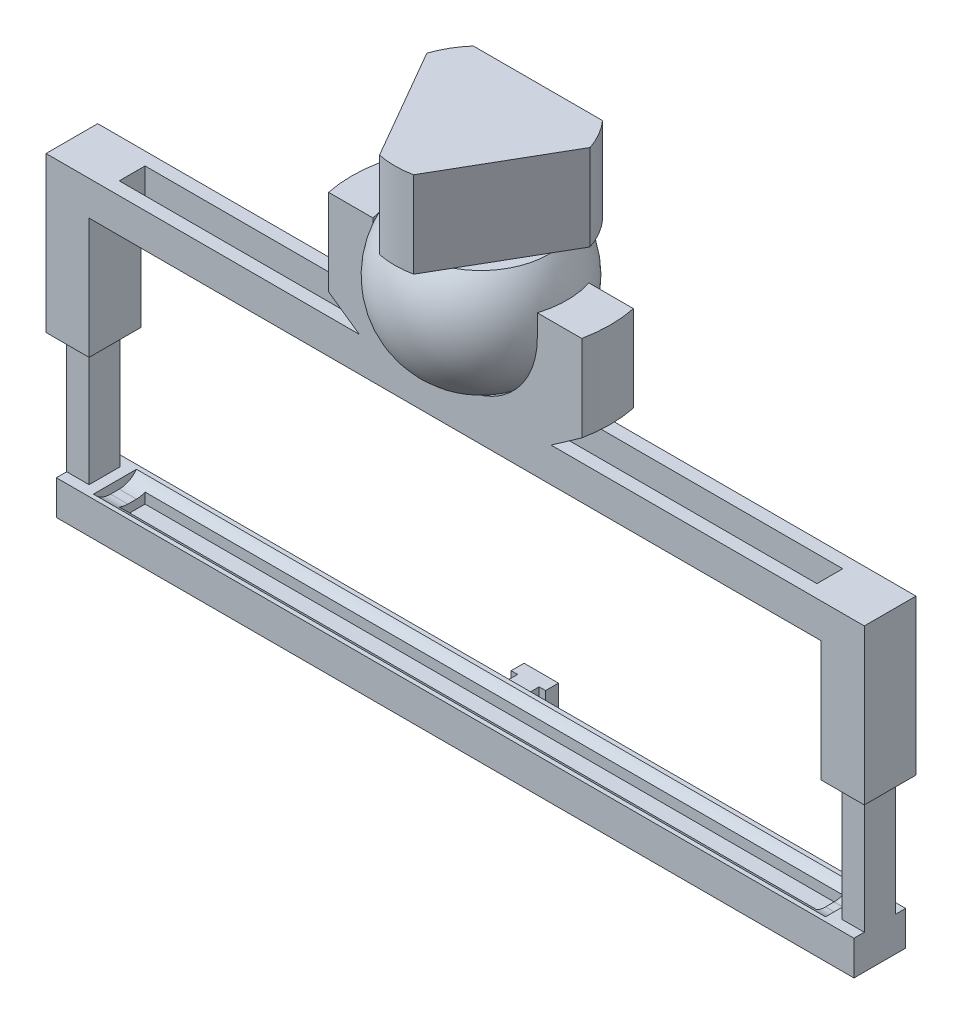
SolidWorks part; units mm, degrees
ref_plane "Front Plane" through (0, 0, 0) normal (0, 0, 1) x (1, 0, 0)
ref_plane "Top Plane" through (0, 0, 0) normal (0, 1, 0) x (1, 0, 0)
ref_plane "Right Plane" through (0, 0, 0) normal (1, 0, 0) x (0, 0, -1)
sketch "Sketch2" plane through (0, 0, 0) normal (0, 0, 1) x (1, 0, 0)
  line L0 (0, 28) -> (0, 0) construction
  line L1 (-85, 36) -> (85, 36)
  line L2 (-85, 36) -> (-85, 28)
  line L3 (-85, 28) -> (85, 28)
  line L4 (85, 36) -> (85, 28)
  line L5 (-85, 28) -> (-85, 0) construction
  line L6 (-85, 0) -> (85, 0) construction
  line L7 (85, 0) -> (85, 28) construction
  point P4 (0, 28)
  dimension "D1" = 170
  dimension "D2" = 8
  dimension "D3" = 28
extrude "Boss-Extrude1" add sketch "Sketch2" along normal mid plane 12
sketch "Sketch3" plane through (0, 28, 0) normal (0, -1, 0) x (1, 0, 0)
  line L1 (-85, 5) -> (85, 5)
  line L2 (-85, 5) -> (-85, -5)
  line L3 (-85, -5) -> (85, -5)
  line L4 (85, 5) -> (85, -5)
  line L6 (-85, 6) -> (-85, -6) construction
  line L7 (85, 6) -> (85, -6) construction
  point P6 (85, 0)
  dimension "D1" = 10
extrude "Cut-Extrude1" cut sketch "Sketch3" against normal blind 2
fillet "Fillet1" radius 5 2 edges at (0, 30, -5) (0, 30, 5)
mirror "Mirror3" about plane through (0, 0, 0) normal (0, 1, 0) of bodies 103
sketch "Sketch4" plane through (0, 36, 0) normal (0, 1, 0) x (1, 0, 0)
  line L0 (-85, -6) -> (-85, 6) construction
  line L1 (-81, 3) -> (81, 3)
  line L2 (-81, 3) -> (-81, -3)
  line L3 (-81, -3) -> (81, -3)
  line L4 (81, 3) -> (81, -3)
  line L5 (85, -6) -> (85, 6) construction
  line L6 (85, 6) -> (-85, 6) construction
  point P8 (81, 0)
  point P9 (85, 0)
  dimension "D1" = 4
  dimension "D2" = 4
  dimension "D3" = 3
extrude "Cut-Extrude2" cut sketch "Sketch4" against normal up to surface (72 mm away) up to face at (0, -36, 0)
sketch "Sketch10" plane through (85, 0, 0) normal (1, 0, 0) x (0, 0, -1)
  line L0 (6, 28) -> (6, 36) construction
  line L1 (-6, 36) -> (6, 36)
  line L2 (-6, 36) -> (-6, 0)
  line L3 (-6, 0) -> (6, 0)
  line L4 (6, 36) -> (6, 0)
extrude "Boss-Extrude6" add sketch "Sketch10" along normal blind 10
sketch "Sketch11" plane through (0, 0, 0) normal (0, -1, 0) x (1, 0, 0)
  line L8 (87, 4) -> (87, -4)
  line L9 (87, -4) -> (93, -4)
  line L10 (93, -4) -> (93, 4)
  line L11 (93, 4) -> (87, 4)
  line L12 (87, 4) -> (87, -4)
  line L13 (87, -4) -> (93, -4)
  line L14 (93, -4) -> (93, 4)
  line L15 (93, 4) -> (87, 4)
  dimension "D1" = 2
extrude "Cut-Extrude4" cut sketch "Sketch11" against normal blind 20
ref_plane "Plane2" through (0, 19, 0) normal (0, -1, 0) x (-1, 0, 0)
sketch "Sketch12" plane through (0, 19, 0) normal (0, -1, 0) x (-1, 0, 0)
  line L8 (-92.6, -3.6) -> (-87.4, -3.6)
  line L9 (-87.4, -3.6) -> (-87.4, 3.6)
  line L10 (-87.4, 3.6) -> (-92.6, 3.6)
  line L11 (-92.6, 3.6) -> (-92.6, -3.6)
  line L12 (-92.6, -3.6) -> (-87.4, -3.6)
  line L13 (-87.4, -3.6) -> (-87.4, 3.6)
  line L14 (-87.4, 3.6) -> (-92.6, 3.6)
  line L15 (-92.6, 3.6) -> (-92.6, -3.6)
  dimension "D1" = 0.4
extrude "Boss-Extrude7" add sketch "Sketch12" along normal up to surface (55 mm away) separate body up to face at (0, -36, 0)
sketch "Sketch13" plane through (0, -36, 0) normal (0, -1, 0) x (1, 0, 0)
  line L0 (92.6, 3.6) -> (92.6, -3.6) construction
  line L1 (85, 6) -> (92.6, 6)
  line L2 (85, 6) -> (85, -6)
  line L3 (85, -6) -> (92.6, -6)
  line L4 (92.6, 6) -> (92.6, -6)
extrude "Boss-Extrude8" add sketch "Sketch13" against normal up to surface (8 mm away) contours L1 L4 L3 L2 up to face at (0, -28, -5.5)
mirror "Mirror4" about plane through (0, 0, 0) normal (1, 0, 0) of "Cut-Extrude4", "Boss-Extrude6"
mirror "Mirror7" about plane through (0, 0, 0) normal (1, 0, 0) of "Boss-Extrude8"
mirror "Mirror9" about plane through (0, 0, 0) normal (1, 0, 0) of bodies 117
sketch "Sketch16" plane through (0, 36, 0) normal (0, 1, 0) x (1, 0, 0)
  line L0 (-2.5, 6) -> (2.5, 6)
  line L14 (95, 6) -> (-95, 6) construction
  line L15 (2.5, 6) -> (2.5, 11)
  line L16 (2.5, 11) -> (4, 11)
  line L17 (4, 11) -> (4, 14)
  line L18 (4, 14) -> (-4, 14)
  line L19 (-4, 14) -> (-4, 11)
  line L20 (-4, 11) -> (-2.5, 11)
  line L21 (-2.5, 11) -> (-2.5, 6)
  point P4 (0, 6)
  point P11 (0, 14)
  dimension "D1" = 5
  dimension "D2" = 3
  dimension "D3" = 5
  dimension "D4" = 8
extrude "Boss-Extrude9" add sketch "Sketch16" against normal up to surface (72 mm away)
sketch "Sketch17" plane through (0, 0, -14) normal (0, 0, -1) x (-1, 0, 0)
  line L0 (-4, -36) -> (-4, 36) construction
  line L1 (-4, 31) -> (4, 31)
  line L2 (-4, 31) -> (-4, -31)
  line L3 (-4, -31) -> (4, -31)
  line L4 (4, 31) -> (4, -31)
  line L5 (4, -36) -> (4, 36) construction
  line L6 (-4, 36) -> (4, 36) construction
  dimension "D1" = 5
  dimension "D2" = 5
extrude "Cut-Extrude5" cut sketch "Sketch17" against normal up to surface (8 mm away) up to face at (60.8333, 21.3333, -6)
sketch "Sketch18" plane through (0, 36, 0) normal (0, 1, 0) x (1, 0, 0)
  line L0 (-5, 6.5) -> (-5, 14.5)
  line L1 (-5, 14.5) -> (5, 14.5)
  line L2 (5, 14.5) -> (5, 6.5)
  line L3 (-2.5, 6) -> (-95, 6) construction
  line L4 (4, 14) -> (-4, 14) construction
  line L5 (4, 11) -> (4, 14) construction
  line L6 (-6.5, 6.5) -> (-6.5, 16)
  line L7 (-6.5, 16) -> (6.5, 16)
  line L8 (6.5, 16) -> (6.5, 6.5)
  line L9 (-6.5, 6.5) -> (-5, 6.5)
  line L10 (5, 6.5) -> (6.5, 6.5)
  point P4 (0, 14.5)
  dimension "D1" = 0.5
  dimension "D2" = 0.5
  dimension "D3" = 1
  dimension "D4" = 1.5
extrude "Boss-Extrude10" add sketch "Sketch18" against normal blind 40 separate body
sketch "Sketch19" plane through (0, -4, 0) normal (0, -1, 0) x (1, 0, 0)
  line L0 (6.5, -6.5) -> (6.5, -16) construction
  line L1 (-6.5, -6.5) -> (6.5, -6.5)
  line L2 (-6.5, -6.5) -> (-6.5, -5)
  line L3 (-6.5, -5) -> (6.5, -5)
  line L4 (6.5, -6.5) -> (6.5, -5)
  line L5 (-85, -5) -> (85, -5) construction
extrude "Boss-Extrude11" add sketch "Sketch19" against normal offset from surface (31.5 mm away) 0.5 up to face at (0, 28, -5.5)
sketch "Sketch20" plane through (0, 28, 0) normal (0, -1, 0) x (1, 0, 0)
  line L1 (-6.65, -4.85) -> (-4.85, -4.85)
  line L2 (-6.65, -4.85) -> (-6.65, -6)
  line L3 (-6.65, -6) -> (-4.85, -6)
  line L4 (-4.85, -4.85) -> (-4.85, -6)
  line L5 (-85, -6) -> (85, -6) construction
  line L6 (-6.5, -16) -> (-6.5, -5) construction
  line L7 (-5, -6.5) -> (-5, -14.5) construction
  line L8 (0, -6.5) -> (0, -16) construction
  line L9 (-5, -6.5) -> (5, -6.5) construction
  line L10 (6.5, -16) -> (-6.5, -16) construction
  line L11 (6.65, -6) -> (4.85, -6)
  line L12 (4.85, -4.85) -> (4.85, -6)
  line L13 (6.65, -4.85) -> (4.85, -4.85)
  line L14 (6.65, -4.85) -> (6.65, -6)
  line L15 (-85, -5) -> (85, -5) construction
  dimension "D1" = 0.15
  dimension "D2" = 0.15
  dimension "D3" = 0.15
extrude "Cut-Extrude6" cut sketch "Sketch20" against normal blind 1
sketch "Sketch21" plane through (0, 27.5, 0) normal (0, 1, 0) x (1, 0, 0)
  line L6 (5, 6.5) -> (6.5, 6.5)
  line L7 (5, 6.5) -> (5, 5)
  line L8 (5, 5) -> (6.5, 5)
  line L9 (6.5, 6.5) -> (6.5, 5)
  line L10 (-5, 6.5) -> (-6.5, 6.5)
  line L11 (-5, 6.5) -> (-5, 5)
  line L12 (-5, 5) -> (-6.5, 5)
  line L13 (-6.5, 6.5) -> (-6.5, 5)
extrude "Boss-Extrude12" add sketch "Sketch21" along normal blind 1
sketch "Sketch22" plane through (0, 36, 0) normal (0, 1, 0) x (1, 0, 0)
  line L0 (95, 6) -> (2.5, 6) construction
  line L1 (4.85, 6) -> (6.65, 6)
  line L2 (4.85, 6) -> (4.85, 4.85)
  line L3 (4.85, 4.85) -> (6.65, 4.85)
  line L4 (6.65, 6) -> (6.65, 4.85)
  line L5 (6.5, 6.5) -> (6.5, 16) construction
  line L6 (5, 14.5) -> (5, 6.5) construction
  line L7 (0, 14) -> (0, 0) construction
  line L8 (4, 14) -> (-4, 14) construction
  line L9 (-4.85, 4.85) -> (-6.65, 4.85)
  line L10 (-6.65, 6) -> (-6.65, 4.85)
  line L11 (-4.85, 6) -> (-6.65, 6)
  line L12 (-4.85, 6) -> (-4.85, 4.85)
  line L13 (6.65, 4.85) -> (4.85, 4.85) construction
  dimension "D2" = 0.15
  dimension "D3" = 0.15
extrude "Cut-Extrude7" cut sketch "Sketch22" against normal up to surface (7.5 mm away) up to face at (-5.75, 28.5, -5.75)
sketch "Sketch23" plane through (0, 28.5, 0) normal (0, 1, 0) x (1, 0, 0)
  line L4 (-6.5, 6.5) -> (-6.5, 5)
  line L5 (-6.5, 5) -> (-5, 5)
  line L6 (-5, 5) -> (-5, 6.5)
  line L7 (-5, 6.5) -> (-6.5, 6.5)
  line L8 (-6.5, 6.5) -> (-6.5, 5)
  line L9 (-6.5, 5) -> (-5, 5)
  line L10 (-5, 5) -> (-5, 6.5)
  line L11 (-5, 6.5) -> (-6.5, 6.5)
  line L12 (5, 6.5) -> (5, 5)
  line L13 (5, 5) -> (6.5, 5)
  line L14 (6.5, 5) -> (6.5, 6.5)
  line L15 (6.5, 6.5) -> (5, 6.5)
  line L16 (5, 6.5) -> (5, 5)
  line L17 (5, 5) -> (6.5, 5)
  line L18 (6.5, 5) -> (6.5, 6.5)
  line L19 (6.5, 6.5) -> (5, 6.5)
  dimension "D1" = 0
  dimension "D2" = 0
extrude "Boss-Extrude13" add sketch "Sketch23" along normal up to surface (7.5 mm away) up to face at (0, 36, 0)
sketch "Sketch24" plane through (0, -36, 0) normal (0, -1, 0) x (1, 0, 0)
  line L0 (-81, 3) -> (-81, -3) construction
  line L1 (-81, 3) -> (-81, -3)
  line L2 (81, -3) -> (81, 3) construction
  line L3 (-81, -3) -> (81, -3) construction
  line L4 (81, 3) -> (-81, 3) construction
  line L5 (81, -3) -> (81, 3)
  line L6 (-81, -3) -> (81, -3)
  line L7 (81, 3) -> (-81, 3)
extrude "Boss-Extrude14" add sketch "Sketch24" against normal blind 4
sketch "Sketch25" plane through (0, 0, 0) normal (0, 0, 1) x (1, 0, 0)
  line L0 (95, 36) -> (-95, 36) construction
  line L1 (17.5, 32) -> (30, 41)
  line L2 (30, 56) -> (20, 56)
  line L3 (-20, 56) -> (-30, 56)
  line L4 (30, 41) -> (30, 56)
  line L5 (17.5, 32) -> (-17.5, 32)
  line L6 (-17.5, 32) -> (-30, 41)
  line L7 (-30, 41) -> (-30, 56)
  line L8 (0, 36) -> (0, 56) construction
  line L9 (0, 36) -> (0, 32)
  line L10 (20, 56) -> (20, 61)
  line L11 (20, 61) -> (30, 61)
  line L12 (30, 61) -> (30, 56)
  arc A0 (-20, 56) -> (20, 56) centre (0, 56) ccw
  point P6 (0, 36)
  point P20 (0, 32)
  dimension "D2" = 40
  dimension "D3" = 4
  dimension "D4" = 15
  dimension "D5" = 15
  dimension "D1" = 10
  dimension "D6" = 10
  dimension "D7" = 35
  dimension "D8" = 10
  dimension "D9" = 5
revolve "Revolve4" add sketch "Sketch25" angle 360 about L8 region at (-19.1087, 42.2923, 0) region at (25, 58.5, 0) other way angle 360
sketch "Sketch26" plane through (-95, 0, 0) normal (-1, 0, 0) x (0, 0, 1)
  line L0 (-6, 32) -> (-30, 32)
  line L1 (-6, 0) -> (-6, 36) construction
  line L2 (-5, 32) -> (-16, 32) construction
  line L3 (-30, 32) -> (-30, 61)
  line L4 (-30, 61) -> (-6, 61)
  line L5 (30, 61) -> (30, 32)
  line L6 (30, 32) -> (6, 32)
  line L7 (6, 32) -> (6, 36)
  line L9 (-6, 36) -> (-6, 32)
  line L10 (-6, 61) -> (-6, 36)
  line L11 (6, 61) -> (6, 36)
  line L12 (6, 61) -> (30, 61)
extrude "Cut-Extrude8" cut sketch "Sketch26" against normal through all
sketch "Sketch27" plane through (0, 0, 0) normal (0, 0, 1) x (1, 0, 0)
  line L0 (0, 75.7) -> (0, 36.3) construction
  circle A0 centre (0, 56) radius 19.7
  arc A1 (-19.0788, 56) -> (19.0788, 56) centre (0, 56) ccw construction
  dimension "D1" = 39.4
revolve "Revolve6" add sketch "Sketch27" angle 360 about L0 region at (-8.3609, 56, 0)
sketch "Sketch28" plane through (0, -4, 0) normal (0, -1, 0) x (1, 0, 0)
  line L4 (6.5, -16) -> (6.5, -5)
  line L5 (6.5, -5) -> (-6.5, -5)
  line L6 (-6.5, -5) -> (-6.5, -16)
  line L7 (-6.5, -16) -> (6.5, -16)
  line L8 (6.5, -16) -> (6.5, -5)
  line L9 (6.5, -5) -> (-6.5, -5)
  line L10 (-6.5, -5) -> (-6.5, -16)
  line L11 (-6.5, -16) -> (6.5, -16)
  dimension "D1" = 0
extrude "Cut-Extrude9" cut sketch "Sketch28" against normal up to surface (36 mm away) up to face at (0, 32, -10.625)
sketch "Sketch29" plane through (0, 28, 0) normal (0, -1, 0) x (1, 0, 0)
  line L1 (-6.65, -6) -> (6.65, -6)
  line L2 (-6.65, -6) -> (-6.65, -5)
  line L3 (-6.65, -5) -> (6.65, -5)
  line L4 (6.65, -6) -> (6.65, -5)
extrude "Boss-Extrude15" add sketch "Sketch29" against normal up to surface (4 mm away) up to face at (0, 32, -5.175)
sketch "Sketch30" plane through (0, 28, 0) normal (0, -1, 0) x (1, 0, 0)
  line L0 (-4, -14) -> (4, -14) construction
  line L1 (4, -14) -> (4, -11) construction
  line L2 (4, -11) -> (2.5, -11) construction
  line L3 (2.5, -11) -> (2.5, -6) construction
  line L4 (-2.5, -6) -> (-2.5, -11) construction
  line L5 (-2.5, -11) -> (-4, -11) construction
  line L6 (-4, -11) -> (-4, -14) construction
  line L7 (-4, -14) -> (4, -14)
  line L8 (4, -14) -> (4, -11)
  line L9 (4, -11) -> (2.5, -11)
  line L10 (2.5, -11) -> (2.5, -6)
  line L11 (-2.5, -6) -> (-2.5, -11)
  line L12 (-2.5, -11) -> (-4, -11)
  line L13 (-4, -11) -> (-4, -14)
  line L14 (-2.5, -6) -> (2.5, -6)
extrude "Boss-Extrude16" add sketch "Sketch30" against normal blind 5 separate body
ref_plane "Plane3" through (0, 68, 0) normal (0, 1, 0) x (1, 0, 0)
sketch "Sketch31" plane through (0, 68, 0) normal (0, 1, 0) x (1, 0, 0)
  circle A0 centre (0, 0) radius 20
  dimension "D1" = 40
extrude "Boss-Extrude17" add sketch "Sketch31" along normal blind 20
sketch "Sketch32" plane through (0, 88, 0) normal (0, 1, 0) x (1, 0, 0)
  line L0 (-15, 13.2288) -> (15, 13.2288)
  circle A0 centre (0, 0) radius 20 construction
  arc A1 (15, 13.2288) -> (-15, 13.2288) centre (0, 0) ccw
  dimension "D1" = 30
extrude "Cut-Extrude10" cut sketch "Sketch32" against normal up to surface (20 mm away) up to face at (-15.6234, 68, 0)
pattern_circular "CirPattern1" count 3 over 360 about axis through (0, 88, 0) along (0, 1, 0) of "Cut-Extrude10"
equation "\"phone length\"= 170"
equation "\"phone Thickness\"= 10"
equation "\"phone height\"= 80"
equation "\"D1@Sketch2\"=\"phone length\""
equation "\"D3@Sketch2\"=\"phone height\"*0.7/2"
equation "\"D1@Boss-Extrude1\"=\"phone Thickness\"+2"
equation "\"D1@Sketch3\"=\"phone Thickness\""
equation "\"D1@Cut-Extrude4\"=\"phone height\"/4"
equation "\"D1@Sketch17\"=5"
equation "\"D1@Boss-Extrude10\"=\"phone height\"*0.5"
